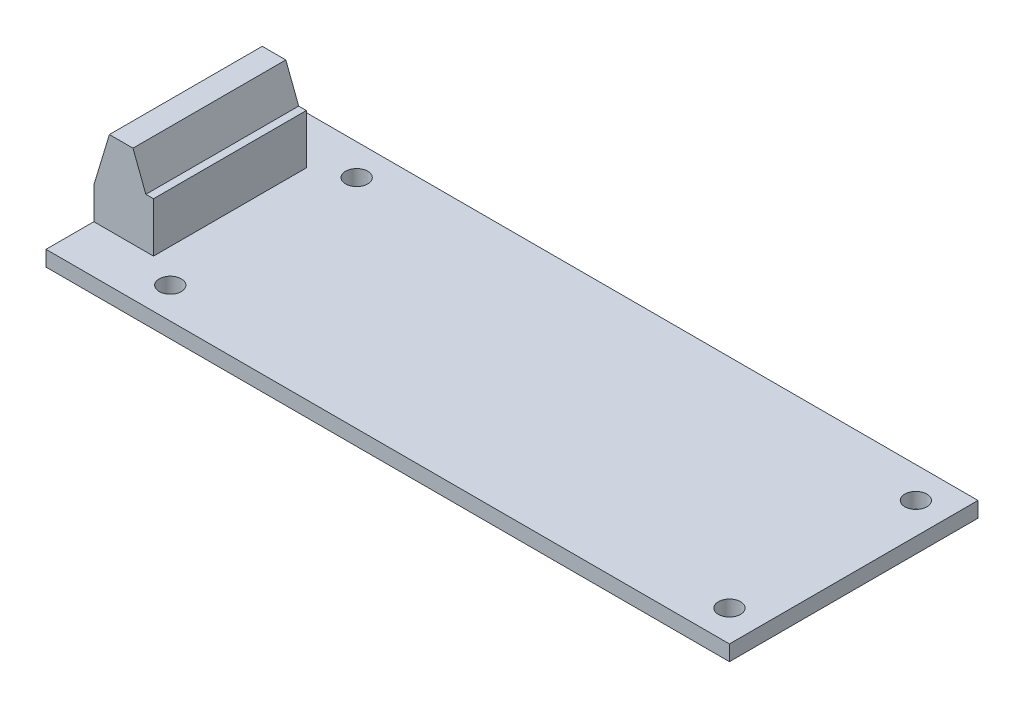
SolidWorks part; units mm, degrees
ref_plane "Front Plane" through (0, 0, 0) normal (0, 0, 1) x (1, 0, 0)
ref_plane "Top Plane" through (0, 0, 0) normal (0, 1, 0) x (1, 0, 0)
ref_plane "Right Plane" through (0, 0, 0) normal (1, 0, 0) x (0, 0, -1)
sketch "Sketch2" plane through (0, 0, 0) normal (0, 1, 0) x (1, 0, 0)
  line L1 (0, 0) -> (69.85, 0)
  line L2 (0, 0) -> (0, 25.4)
  line L3 (0, 25.4) -> (69.85, 25.4)
  line L4 (69.85, 0) -> (69.85, 25.4)
  dimension "D1" = 69.85
  dimension "D2" = 25.4
extrude "Boss-Extrude1" add sketch "Sketch2" along normal blind 1.5748
hole_wizard "Tap Drill for #4-40 Tap1" positions "3DSketch1" profile "Sketch3" hole size "#4-40" standard "ANSI Inch" end condition through all
sketch3d "3DSketch1"
  line L0 (69.85, 1.5748, 0) -> (69.85, 1.5748, -25.4) construction
  line L1 (69.85, 1.5748, -25.4) -> (0, 1.5748, -25.4) construction
  line L2 (0, 1.5748, 0) -> (69.85, 1.5748, 0) construction
  line L3 (0, 1.5748, -25.4) -> (0, 1.5748, 0) construction
  point P0 (9.525, 1.5748, -22.225)
  point P2 (9.525, 1.5748, -3.175)
  point P4 (66.675, 1.5748, -3.175)
  point P6 (66.675, 1.5748, -22.225)
  dimension "D1" = 3.175
  dimension "D2" = 3.175
  dimension "D3" = 3.175
  dimension "D4" = 3.175
  dimension "D5" = 3.175
  dimension "D6" = 3.175
  dimension "D7" = 9.525
  dimension "D8" = 9.525
sketch "Sketch3" plane through (9.525, 1.5748, -22.225) normal (1, 0, 0) x (0, 0, 1)
  line L0 (0, 0) -> (0, 1.5748)
  line L1 (0, 1.5748) -> (1.1303, 1.5748)
  line L2 (1.1303, 1.5748) -> (1.1303, 0)
  line L5 (1.1303, 0) -> (0, 0)
  line L11 (0, -6.35) -> (0, 107.95) construction
  dimension "Thru Hole Dia." = 2.2606
  dimension "Thru Hole Depth" = 1.5748
ref_plane "Plane1" through (0, 0, -12.7) normal (0, 0, 1) x (1, 0, 0)
sketch "Sketch4" plane through (0, 0, -12.7) normal (0, 0, 1) x (1, 0, 0)
  line L0 (0, 1.5748) -> (0, 4.8179)
  line L1 (0, 4.8179) -> (1.5885, 10.0838)
  line L2 (1.5885, 10.0838) -> (3.9995, 10.0838)
  line L3 (3.9995, 10.0838) -> (5.315, 6.6548)
  line L4 (5.315, 6.6548) -> (6.096, 6.6548)
  line L5 (6.096, 6.6548) -> (6.096, 1.5748)
  line L6 (6.096, 1.5748) -> (0, 1.5748)
  line L8 (0, 1.5748) -> (69.85, 1.5748) construction
  point P2 (6.4625, 6.6051)
  point P8 (5.0186, 6.6247)
  point P9 (5.5798, 6.6399)
  point P10 (2.4259, 8.5223)
  point P11 (2.1279, 8.7375)
  point P12 (2.794, 10.0838)
  point P13 (2.3253, 8.6317)
  point P14 (5.6319, 6.6548)
  point P15 (3.8425, 8.5899)
  point P18 (5.4398, 10.0838)
  point P20 (5.4088, 6.6548)
  point P21 (0, 4.8179)
  point P22 (5.315, 6.6548)
  dimension "D1" = 5.08
  dimension "D2" = 6.096
  dimension "D3" = 2.794
  dimension "D4" = 8.509
extrude "Boss-Extrude2" add sketch "Sketch4" along normal mid plane 15.621
